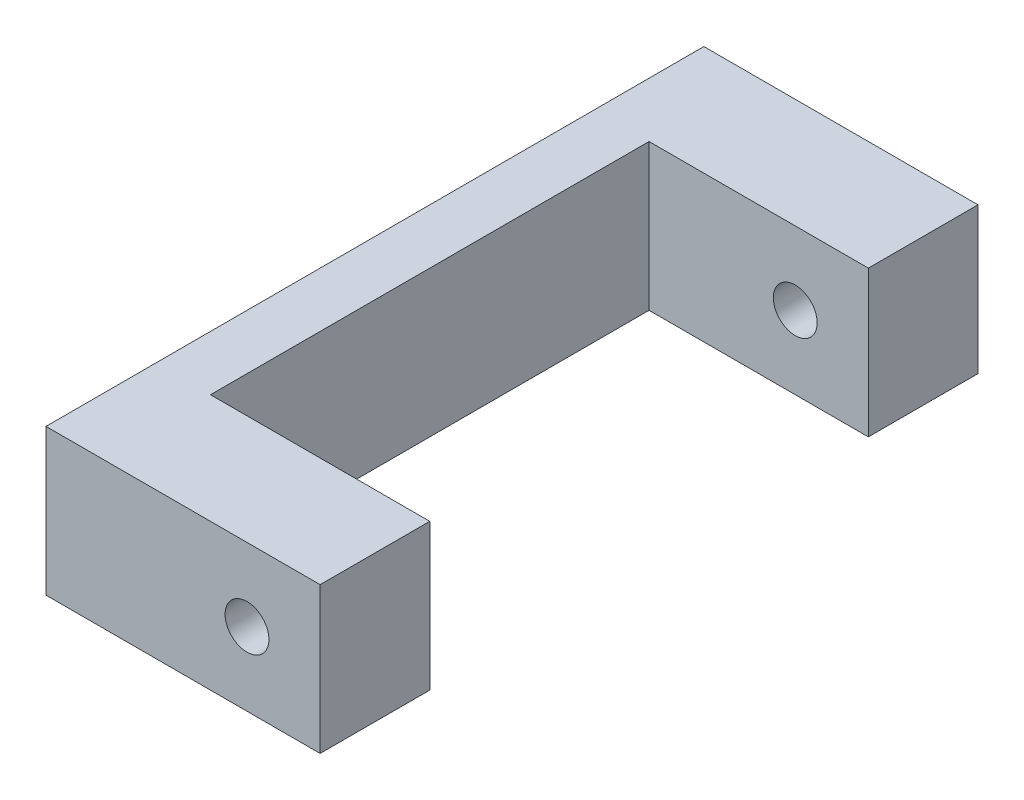
SolidWorks part; units mm, degrees
material "1023 Carbon Steel Sheet (SS)"
ref_plane "Front Plane" through (0, 0, 0) normal (0, 0, 1) x (1, 0, 0)
ref_plane "Top Plane" through (0, 0, 0) normal (0, 1, 0) x (1, 0, 0)
ref_plane "Right Plane" through (0, 0, 0) normal (1, 0, 0) x (0, 0, -1)
sketch "Sketch1" plane through (0, 0, 0) normal (1, 0, 0) x (0, 0, -1)
  line L1 (-90, -20) -> (90, -20)
  line L2 (-90, -20) -> (-90, 20)
  line L3 (-90, 20) -> (90, 20)
  line L4 (90, -20) -> (90, 20)
  line L5 (-90, -20) -> (90, 20) construction
  line L6 (-90, 20) -> (90, -20) construction
  line L7 (-60, -20) -> (60, -20)
  line L8 (-60, -20) -> (-60, 20)
  line L9 (-60, 20) -> (60, 20)
  line L10 (60, -20) -> (60, 20)
  line L11 (-60, -20) -> (60, 20) construction
  line L12 (-60, 20) -> (60, -20) construction
  point P0 (0, 0)
  point P6 (0, 0)
  dimension "D2" = 40
  dimension "D3" = 30
  dimension "D1" = 120
extrude "Boss-Extrude1" add sketch "Sketch1" against normal blind 15 contours L1 L8 L3 L2 | L1 L10 L3 L8 | L10 L1 L4 L3 region at (0, 0, 75) region at (0, 0, 0) region at (0, 0, -75)
extrude "Boss-Extrude2" add sketch "Sketch1<3>" along normal blind 60 contours L1 L8 L3 L2 | L10 L1 L4 L3 region at (0, 0, 75) region at (0, 0, -75)
sketch "Sketch1<3>" plane through (0, 0, 0) normal (1, 0, 0) x (0, 0, -1) same geometry as "Sketch1"
sketch "Sketch2" plane through (0, 0, 60) normal (0, 0, -1) x (-1, 0, 0)
  line L0 (-40, 20) -> (-40, -20) construction
  line L1 (-60, 20) -> (0, 20) construction
  line L2 (-60, -20) -> (0, -20) construction
  line L3 (0, -20) -> (0, 20) construction
  circle A0 centre (-40, 0) radius 6
  dimension "D2" = 12
  dimension "D1" = 40
extrude "Cut-Extrude1" cut sketch "Sketch2" against normal through all both and the other way through all
equation "\"D1@Sketch1\"=4+\"CarriageWidth\"+\"StrutWidth\"*4"
equation "\"StrutWidth\"= 15"
equation "\"CarriageWidth\"= 56"
